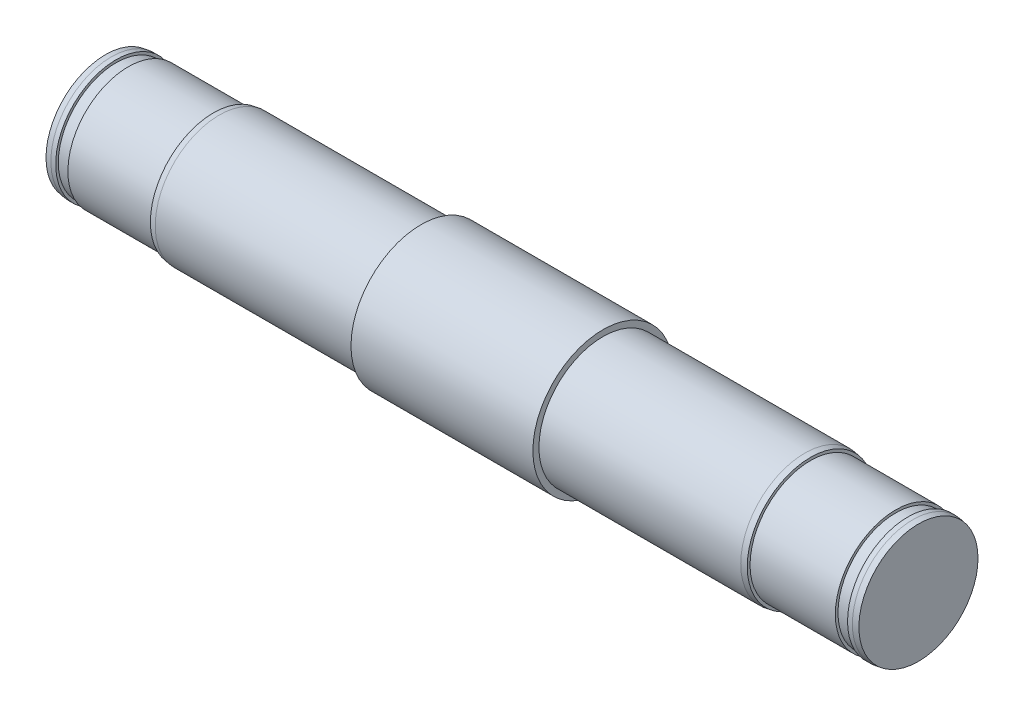
SolidWorks part; units mm, degrees
material "Простая углеродистая сталь"
ref_plane "Спереди" through (0, 0, 0) normal (0, 0, 1) x (1, 0, 0)
ref_plane "Сверху" through (0, 0, 0) normal (0, 1, 0) x (1, 0, 0)
ref_plane "Справа" through (0, 0, 0) normal (1, 0, 0) x (0, 0, -1)
sketch "Эскиз1" plane through (0, 0, 0) normal (0, 0, 1) x (1, 0, 0)
  line L0 (0, 0) -> (0, 14.5)
  line L1 (0, 14.5) -> (16, 14.5)
  line L2 (16, 14.5) -> (16, 13.25)
  line L3 (52.5, 12.5) -> (71.5, 12.5)
  line L4 (71.5, 12.5) -> (71.5, 0)
  line L6 (0, 0) -> (71.5, 0)
  line L7 (16, 13.25) -> (52.5, 13.25)
  line L8 (52.5, 13.25) -> (52.5, 12.5)
  dimension "D1" = 16
  dimension "D2" = 71.5
  dimension "D3" = 36.5
  dimension "D4" = 14.5
  dimension "D5" = 12.5
  dimension "D6" = 13.25
revolve "Повернуть1" add sketch "Эскиз1" angle 360 about L6
mirror "Зеркальное отражение1" about plane through (0, 0, 0) normal (1, 0, 0) of bodies 103
chamfer "Фаска1" distance 1 angle 10 2 edges at (71.5, 0, 12.5) (-71.5, 0, 12.5) first distance on face at (52.5, 0, 12.5) first distance on face at (-52.5, 0, 12.5)
ref_axis "Ось1" through (58.1884, 0, 0) along (-1, 0, 0)
ref_axis "Ось2" through (-66, 0, 0) along (1, 0, 0)
chamfer "Фаска3" distance 1 angle 10 2 edges at (52.5, 0, 13.25) (-52.5, 0, 13.25) first distance on face at (16, 0, 13.25) first distance on face at (-16, 0, 13.25)
sketch "Эскиз2" plane through (0, 0, 0) normal (0, 0, 1) x (1, 0, 0)
  line L0 (70.5, 12.5) -> (52.5, 12.5) construction
  line L1 (67.5, 11.95) -> (69.65, 11.95)
  line L2 (67.5, 11.95) -> (67.5, 13.05)
  line L3 (67.5, 13.05) -> (69.65, 13.05)
  line L4 (69.65, 11.95) -> (69.65, 13.05)
  line L5 (67.5, 11.95) -> (69.65, 13.05) construction
  line L6 (67.5, 13.05) -> (69.65, 11.95) construction
  line L7 (52.5, -13.0737) -> (52.5, 13.0737) construction
  line L8 (0, 0) -> (71.5, 0) construction
  line L9 (71.5, -12.3237) -> (71.5, 12.3237) construction
  point P0 (68.575, 12.5)
  dimension "D1" = 2.15
  dimension "D2" = 11.95
  dimension "D3" = 15
revolve "Вырез-Повернуть1" cut sketch "Эскиз2" angle 360 about L8
mirror "Зеркальное отражение2" about plane through (0, 0, 0) normal (1, 0, 0) of "Вырез-Повернуть1"
scale "Scale4" scale about origin uniform scaling no x scale factor 0.8 y scale factor 0.68 z scale factor 0.68
